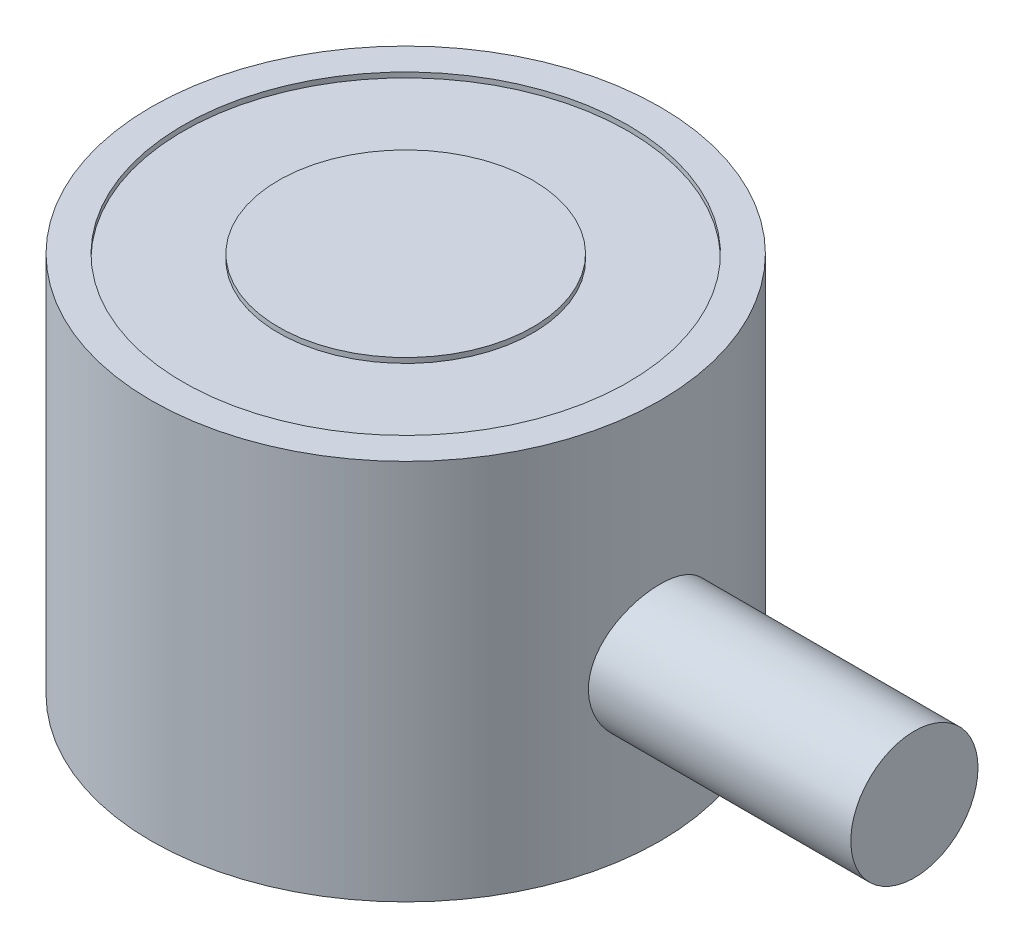
SolidWorks part; units mm, degrees
ref_plane "Front Plane" through (0, 0, 0) normal (0, 0, 1) x (1, 0, 0)
ref_plane "Top Plane" through (0, 0, 0) normal (0, 1, 0) x (1, 0, 0)
ref_plane "Right Plane" through (0, 0, 0) normal (1, 0, 0) x (0, 0, -1)
sketch "Sketch1" plane through (0, 0, 0) normal (0, 1, 0) x (1, 0, 0)
  circle A0 centre (0, 0) radius 12.7
  dimension "A" = 25.4
extrude "Boss-Extrude1" add sketch "Sketch1" along normal blind 19.05
sketch "Sketch2" plane through (0, 0, 0) normal (0, 0, 1) x (1, 0, 0)
  line L0 (-11.1125, 19.05) -> (-11.1125, 18.796)
  line L1 (-11.1125, 18.796) -> (-6.35, 18.796)
  line L2 (-6.35, 18.796) -> (-6.35, 19.05)
  line L3 (12.7, 19.05) -> (-12.7, 19.05) construction
  line L4 (-6.35, 19.05) -> (-11.1125, 19.05)
  line L5 (0, 0) -> (0, 19.05) construction
  line L6 (-12.7, 19.05) -> (-12.7, 0) construction
  dimension "D1" = 1.5875
  dimension "D2" = 4.7625
  dimension "D3" = 0.254
revolve "Cut-Revolve1" cut sketch "Sketch2" angle 360 about L5
sketch "Sketch3" plane through (0, 0, 0) normal (0, -1, 0) x (1, 0, 0)
  circle A0 centre (0, 0) radius 2.413
  point P3 (-2.413, 0)
  point P4 (2.413, 0)
  point P5 (0, 0)
  dimension "Hole Dia." = 4.826
extrude "Cut-Extrude1" cut sketch "Sketch3" against normal blind 9.525
sketch "Sketch4" plane through (0, 0, 0) normal (0, -1, 0) x (1, 0, 0)
  circle A1 centre (0, 0) radius 2.413
  circle A2 centre (0, 0) radius 2.413
  point P0 (-2.413, 0)
  dimension "D1" = 0
curve "Helix/Spiral1" pitch 0.7937 height 10.3188 turns 13 parameters "Pitch"=0.7937
sketch "Sketch5" plane through (0, 0, 0) normal (0, 0, 1) x (1, 0, 0)
  line L0 (-2.4989, 0.0496) -> (-2.4989, -0.7441) construction
  line L1 (-2.4989, -0.7441) -> (-1.8115, -0.3473) construction
  line L2 (-1.8115, -0.3473) -> (-2.4989, 0.0496) construction
  line L3 (-2.413, 0) -> (-2.413, -0.6945) construction
  line L4 (-1.8974, -0.2977) -> (-1.8974, -0.3969) construction
  line L5 (-1.8115, -0.3473) -> (-1.8974, -0.3473) construction
  line L6 (-1.8974, -0.3473) -> (-1.9834, -0.3473) construction
  line L7 (-2.413, -0.3473) -> (-2.4989, -0.3473) construction
  line L8 (-2.456, -0.7193) -> (-2.456, 0.0248)
  line L9 (-2.456, 0.0248) -> (-1.9834, -0.248)
  line L10 (-1.9834, -0.248) -> (-1.9834, -0.4465)
  line L11 (-1.9834, -0.4465) -> (-2.456, -0.7193)
  point P16 (-2.456, -0.3473)
  dimension "D1" = 0.7937
  dimension "D2" = 0.0992
sketch "Sketch6" plane through (0, 0, 0) normal (0, -1, 0) x (1, 0, 0)
  circle A0 centre (0, 0) radius 2.4989
sweep "Sweep1" add profiles "Sketch5" path "Helix/Spiral1"
extrude "Cut-Extrude2" cut sketch "Sketch6" against normal through all draft 45 and the other way through all
sketch "Sketch7" plane through (0, 0, 0) normal (1, 0, 0) x (0, 0, -1)
  line L0 (0, 7.9375) -> (0, 0) construction
  circle A0 centre (0, 7.9375) radius 3.175
  dimension "Wire Dia." = 6.35
  dimension "G" = 4.7625
sketch "Sketch8" plane through (0, 0, 0) normal (0, 0, 1) x (1, 0, 0)
  line L0 (0, 7.9375) -> (25.4, 7.9375) construction
  line L1 (12.7, 0) -> (12.7, 19.05) construction
  dimension "D1" = 12.7
extrude "Boss-Extrude2" add sketch "Sketch7" against normal up to surface (13.1033 mm away) from vertex at 25.4 starting at point (25.4, 7.9375, 0)
sketch "Sketch9" plane through (0, 0, 0) normal (0, 0, 1) x (1, 0, 0)
  line L0 (-2.413, 0) -> (-2.413, 9.525) construction
  line L1 (-2.413, 9.525) -> (2.413, 9.525) construction
  line L2 (2.413, 9.525) -> (2.413, 0) construction
  line L3 (-2.413, 9.525) -> (0.759, 9.525) construction
equation "\"D3@Helix/Spiral1\" = \"Pitch@Helix/Spiral1\" + \"Hole Depth@Cut-Extrude1\""
equation "\"D1@Sketch5\" = \"Pitch@Helix/Spiral1\""
equation "\"D2@Sketch5\" = \"D1@Sketch5\" / 8"
